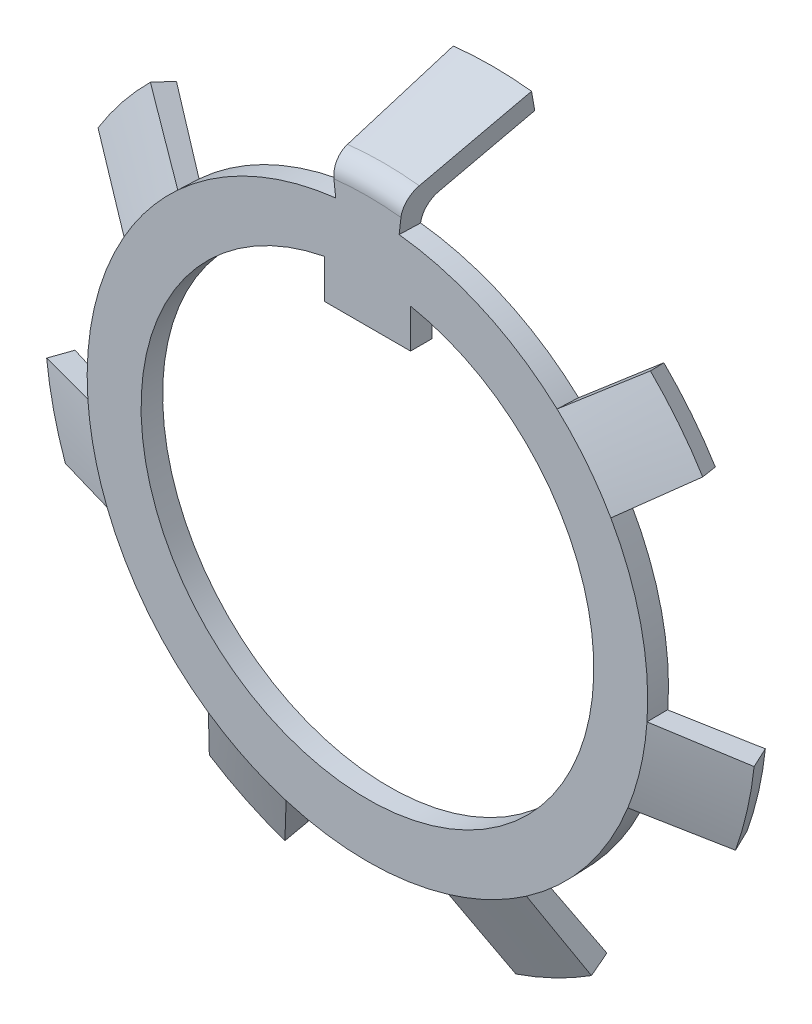
SolidWorks part; units mm, degrees
ref_plane "Front Plane" through (0, 0, 0) normal (0, 0, 1) x (1, 0, 0)
ref_plane "Top Plane" through (0, 0, 0) normal (0, 1, 0) x (1, 0, 0)
ref_plane "Right Plane" through (0, 0, 0) normal (1, 0, 0) x (0, 0, -1)
sketch "Sketch1" plane through (0, 0, 0) normal (1, 0, 0) x (0, 0, -1)
  line L0 (-1, 0) -> (23.0727, 0) construction
  line L1 (-1, 7.5) -> (-1, 13)
  line L2 (-1, 13) -> (0.529, 16.5)
  line L3 (0.529, 16.5) -> (1.4454, 16.0997)
  line L4 (1.4454, 16.0997) -> (0, 13)
  line L5 (0, 13) -> (0, 7.5)
  line L6 (0, 7.5) -> (-1, 7.5)
  dimension "D1" = 15
  dimension "D2" = 1
  dimension "D3" = 25
  dimension "D4" = 33
  dimension "D5" = 26
revolve "Revolve1" add sketch "Sketch1" angle 360 about L0
sketch "Sketch2" plane through (0, 0, 0) normal (0, 0, 1) x (1, 0, 0)
  line L0 (-2, 8.5) -> (-2, 10.3078)
  line L1 (-2, 8.5) -> (2, 8.5)
  line L5 (2, 8.5) -> (2, 10.3078)
  arc A0 (-2, 10.3078) -> (2, 10.3078) centre (0, 0) ccw
  point P1 (0, 8.5)
  dimension "D2" = 4
  dimension "D3" = 10.5
  dimension "D1" = 8.5
extrude "Cut-Extrude2" cut sketch "Sketch2" against normal through all both and the other way through all
sketch "Sketch3" plane through (0, 0, 1) normal (0, 0, 1) x (1, 0, 0)
  line L0 (0, 16.5) -> (0, 13) construction
  line L1 (14.0521, 8.6481) -> (11.2898, 6.4452)
  line L2 (2, 16.3783) -> (2, 12.8452)
  line L3 (-2, 16.3783) -> (-2, 12.8452)
  line L6 (11.5581, 11.7754) -> (8.7958, 9.5725)
  line L7 (15.5227, -5.5944) -> (12.0781, -4.8082)
  line L8 (16.4127, -1.6947) -> (12.9682, -0.9085)
  line L9 (5.3044, -15.6241) -> (3.7714, -12.4409)
  line L10 (8.9082, -13.8886) -> (7.3753, -10.7054)
  line L11 (-8.9082, -13.8886) -> (-7.3753, -10.7054)
  line L12 (-5.3044, -15.6241) -> (-3.7714, -12.4409)
  line L13 (-16.4127, -1.6947) -> (-12.9682, -0.9085)
  line L14 (-15.5227, -5.5944) -> (-12.0781, -4.8082)
  line L15 (-11.5581, 11.7754) -> (-8.7958, 9.5725)
  line L16 (-14.0521, 8.6481) -> (-11.2898, 6.4452)
  circle A0 centre (0, 0) radius 16.5 construction
  circle A1 centre (0, 0) radius 16.5
  circle A2 centre (0, 0) radius 13
  circle A3 centre (0, 0) radius 13 construction
  circle A4 centre (0, 0) radius 13
  circle A5 centre (0, 0) radius 13
  circle A6 centre (0, 0) radius 13
  circle A7 centre (0, 0) radius 13
  circle A8 centre (0, 0) radius 13
  circle A9 centre (0, 0) radius 13
  circle A10 centre (0, 0) radius 13 construction
  point P39 (0, 0)
  circle M12 centre (0, 0) radius 13
  dimension "D2" = 4
  dimension "D1" = 7
extrude "Cut-Extrude4" cut sketch "Sketch3" against normal blind 10 draft 2 contours A2 A1 L2 | A1 L0 A2 L2 | L0 A1 L3 A2 | A2 L3 A1 | A2 A1 | A2 A1 | A2 A1 | L8 A1 L1 M12 | L16 A1 L13 M12 region at (1.0016, 14.7039, 1) region at (-1.0016, 14.7039, 1) region at (6.3377, 13.1604, 1) region at (-6.3377, 13.1604, 1) region at (14.2407, 3.2503, 1) region at (-14.2407, 3.2503, 1) region at (-11.4202, -9.1073, 1) region at (11.4202, -9.1073, 1) region at (0, -14.6069, 1) draft outward yes
sketch "Sketch4" plane through (0, 0, 0) normal (1, 0, 0) x (0, 0, -1)
  line L0 (-1, 0) -> (23.0727, 0) construction
  line L1 (-1, 10) -> (-1, 14.5)
  line L2 (-1, 14.5) -> (4.7956, 16.0529)
  line L3 (4.7956, 16.0529) -> (5.0544, 15.087)
  line L4 (5.0544, 15.087) -> (0, 13.7327)
  line L5 (0, 13.7327) -> (0, 10)
  line L6 (0, 10) -> (-1, 10)
  dimension "D1" = 20
  dimension "D2" = 1
  dimension "D3" = 75
  dimension "D4" = 6
  dimension "D5" = 29
revolve "Revolve3" add sketch "Sketch4" angle 13 mid plane about L0
fillet "Fillet1" radius 1 2 edges at (0, 14.5, 1) (0, 13.7327, 0)
equation "\"d_ext_rouleau\"= 90"
equation "\"epaisseur_rouleau\"=80"
equation "\"alesage-rouleau\"= 52"
equation "\"jeu_dent_rouleau\"= 2"
equation "\"profondeur_dent_rouleau\"=4"
equation "\"n_dent_roueau\"= 15"
equation "\"d_ext_roulement_rouleau\"= 42"
equation "\"d_int_roulement_rouleau\"= 20"
equation "\"B_roulement_rouleau\"= 12"
equation "\"r_roulement_rouleau\"= 0.6"
equation "\"d_bille_roulement_rouleau\"= 8"
equation "\"F_anneau_alesage_rouleau\"=1.85"
equation "\"G_anneau_alesage_rouleau\"=47.5"
equation "\"K_anneau_alesage_rouleau\"=3.75"
equation "\"d_vis_flasque_rouleau\"=5"
equation "\"l-x_vis_flasque_rouleau\"=4"
equation "\"g_anneau_arbre_rouleau\"=19"
equation "\"f_anneau_arbre_rouleau\"=1.3"
equation "\"k_anneau_arbre_rouleau\"=1.5"
equation "\"entrax_vis_rouleau\"=65"
equation "\"d_granulat\"= 8"
equation "\"h_matrice\"= 22"
equation "\"d_matrice\"= 220"
equation "\"zone_vide_matrice\" = 48"
equation "\"d_alesage_matrice\"=20"
equation "\"a_clavette_alesage_matrice\"=6"
equation "\"B_roulement_matrice\"= 12"
equation "\"d_ext_roulement_matrice\"= 42"
equation "\"d_int_roulement_matrice\"= 20"
equation "\"r_roulement_matrice\"= 1"
equation "\"h_epaulement_arbre_matrice\" = 80"
equation "\"h_polie_matrice\" = 40"
equation "\"l_arbre_matrice\" = 300"
equation "\"d_int_ecrou_encouch_matrice\" = 20"
equation "\"d_ext_ecrou_encouch_matrice\" = 32"
equation "\"b_ecrou_encouch_matrice\" = 6"
equation "\"s_ecrou_encouch_matrice\" = 4"
equation "\"G_ecrou_encouch_matrice\" = 1"
equation "\"D2@Sketch1\"=\"G_ecrou_encouch_matrice\""
equation "\"D2@Sketch3\"=\"s_ecrou_encouch_matrice\""
equation "\"E_ecrou_encouch_matrice\" = 4"
equation "\"D2@Sketch2\"=\"E_ecrou_encouch_matrice\""
